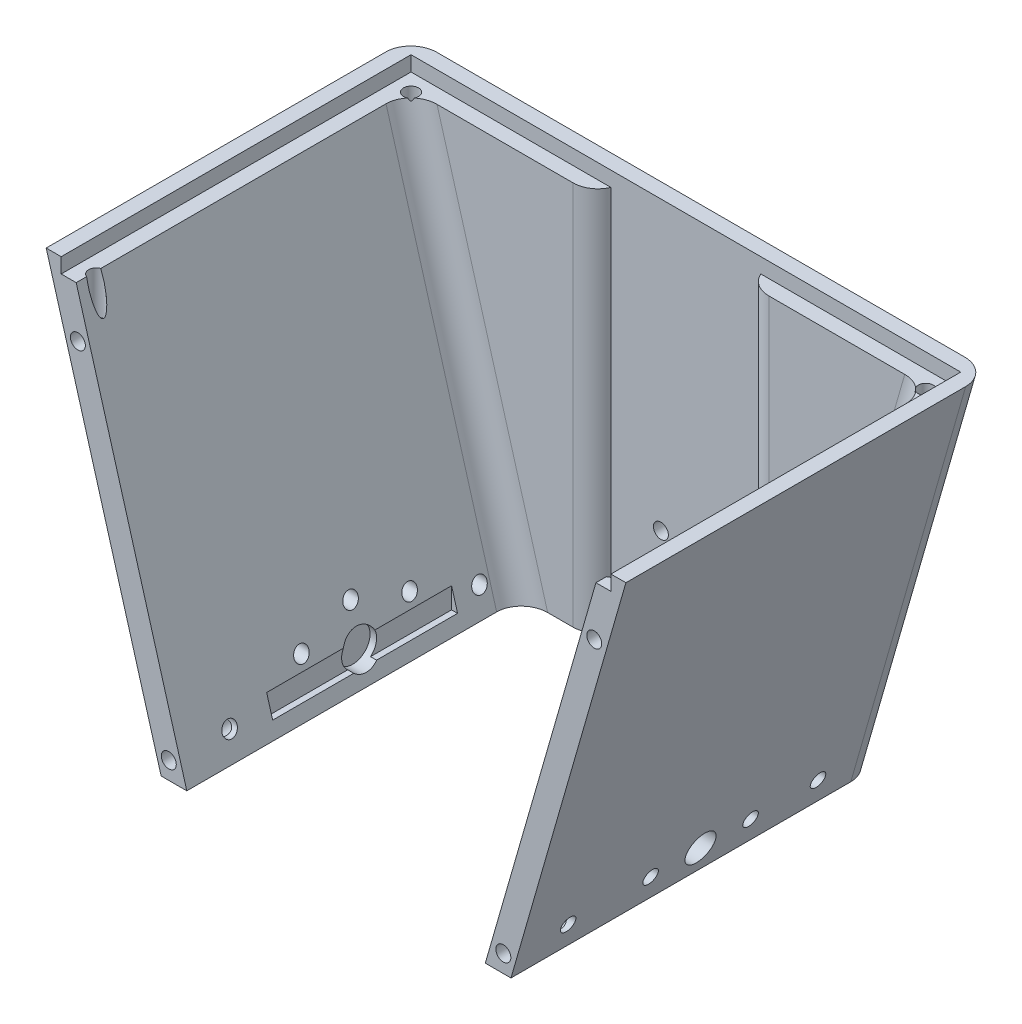
SolidWorks part; units mm, degrees
ref_plane "Front Plane" through (0, 0, 0) normal (0, 0, 1) x (1, 0, 0)
ref_plane "Top Plane" through (0, 0, 0) normal (0, 1, 0) x (1, 0, 0)
ref_plane "Right Plane" through (0, 0, 0) normal (1, 0, 0) x (0, 0, -1)
sketch "Sketch1" plane through (0, 0, 0) normal (0, 0, 1) x (1, 0, 0)
  line L0 (-70.4949, 0) -> (45.5051, 0)
  line L1 (-12.4949, -80) -> (22.5051, -80)
  line L2 (-12.4949, -80) -> (-47.4949, -80)
  line L3 (-70.4949, 0) -> (-47.4949, -80)
  line L4 (-12.4949, 0) -> (-12.4949, -303.8109) construction
  line L5 (45.5051, 0) -> (22.5051, -80)
  dimension "D1" = 116
  dimension "D2" = 35
  dimension "D3" = 35
  dimension "D4" = 80
  dimension "D5" = 73.96
  dimension "D6" = 73.96
extrude "Boss-Extrude1" add sketch "Sketch1" along normal blind 76
sketch "Sketch2" plane through (0, 0, 0) normal (0, 1, 0) x (1, 0, 0)
  line L0 (45.5051, 0) -> (-70.4949, 0) construction
  line L1 (-67.4949, -3) -> (42.5051, -3)
  line L2 (-67.4949, -3) -> (-67.4949, -73)
  line L3 (-67.4949, -73) -> (42.5051, -73)
  line L4 (42.5051, -3) -> (42.5051, -73)
  line L5 (45.5051, -76) -> (45.5051, 0) construction
  line L6 (45.5051, -76) -> (-70.4949, -76) construction
  line L7 (-70.4949, -76) -> (-70.4949, 0) construction
  dimension "D1" = 3
  dimension "D2" = 3
  dimension "D3" = 3
  dimension "D4" = 3
  dimension "D5" = 110
  dimension "D6" = 70
extrude "Cut-Extrude1" cut sketch "Sketch2" against normal blind 3
sketch "Sketch3" plane through (0, 0, 76) normal (0, 0, 1) x (1, 0, 0)
  line L0 (-42.0698, -81) -> (17.08, -81)
  line L1 (17.08, -81) -> (39.5051, -3)
  line L2 (39.5051, -3) -> (-64.4949, -3)
  line L3 (-64.4949, -3) -> (-42.0698, -81)
  line L5 (45.5051, 0) -> (-70.4949, 0) construction
  line L6 (-12.4949, -3) -> (-12.4949, -72.5382) construction
  line L7 (-67.4949, -3) -> (42.5051, -3) construction
  point P9 (-12.4949, 0)
  dimension "D1" = 73.96
  dimension "D2" = 73.96
  dimension "D3" = 104
  dimension "D4" = 0
  dimension "D5" = 0
  dimension "D6" = 78
extrude "Cut-Extrude2" cut sketch "Sketch3" against normal blind 70
sketch "Sketch4" plane through (0, 0, 0) normal (0, 1, 0) x (1, 0, 0)
  line L0 (45.5051, -76) -> (45.5051, 0) construction
  line L1 (-70.4949, -76) -> (45.5051, -76)
  line L2 (-70.4949, -76) -> (-70.4949, -73)
  line L3 (-70.4949, -73) -> (45.5051, -73)
  line L4 (45.5051, -76) -> (45.5051, -73)
extrude "Cut-Extrude3" cut sketch "Sketch4" against normal blind 95
fillet "Fillet1" radius 5 1 edges at (28.4363, -41.5, 6)
fillet "Fillet2" radius 5 1 edges at (-53.4261, -41.5, 6)
sketch "Sketch6" plane through (0, -3, 0) normal (0, 1, 0) x (1, 0, 0)
  line L0 (42.5051, -73) -> (42.5051, -3) construction
  line L1 (42.5051, -3) -> (-67.4949, -3) construction
  line L2 (-67.4949, -3) -> (-67.4949, -73) construction
  line L3 (-67.4949, -3) -> (-67.4949, -73) construction
  line L4 (-67.4949, -73) -> (-64.4949, -73) construction
  line L5 (42.5051, -73) -> (42.5051, -3) construction
  line L6 (39.5051, -73) -> (42.5051, -73) construction
  circle A0 centre (39.0051, -6.5) radius 1.5
  circle A1 centre (-63.9949, -6.5) radius 1.5
  circle A2 centre (-63.9949, -69.5) radius 1.5
  circle A3 centre (39.0051, -69.5) radius 1.5
  dimension "D1" = 3.5
  dimension "D2" = 3.5
  dimension "D3" = 3
  dimension "D4" = 3.5
  dimension "D5" = 3.5
  dimension "D6" = 3
  dimension "D7" = 3.5
  dimension "D8" = 3.5
  dimension "D9" = 3.5
  dimension "D10" = 3
  dimension "D11" = 3.5
  dimension "D12" = 3
extrude "Cut-Extrude4" cut sketch "Sketch6" against normal blind 10
sketch "Sketch7" plane through (0, -3, 0) normal (0, 1, 0) x (1, 0, 0)
  line L0 (34.3025, -6) -> (-59.2924, -6) construction
  line L1 (-27.4949, -9) -> (2.5051, -9)
  line L2 (-27.4949, -9) -> (-27.4949, -3)
  line L3 (-27.4949, -3) -> (2.5051, -3)
  line L4 (2.5051, -9) -> (2.5051, -3)
  line L5 (-27.4949, -9) -> (2.5051, -3) construction
  line L6 (-27.4949, -3) -> (2.5051, -9) construction
  line L7 (42.5051, -3) -> (-67.4949, -3) construction
  point P0 (-12.4949, -6)
  dimension "D1" = 30
extrude "Cut-Extrude5" cut sketch "Sketch7" against normal blind 93
fillet "Fillet3" radius 5 1 edges at (34.0051, -40, 0)
fillet "Fillet4" radius 5 1 edges at (-58.9949, -40, 0)
sketch "Sketch8" plane through (0, 0, 0) normal (0, 0, -1) x (-1, 0, 0)
  line L0 (12.4949, -80) -> (12.4949, -69) construction
  line L1 (42.2924, -80) -> (-17.3025, -80) construction
  line L3 (20.9949, -54) -> (3.9949, -54) construction
  line L4 (20.9949, -54) -> (20.9949, -69) construction
  line L5 (20.9949, -69) -> (3.9949, -69) construction
  line L6 (3.9949, -54) -> (3.9949, -69) construction
  circle A0 centre (7.4949, -65.5) radius 1.5
  circle A1 centre (7.4949, -57.5) radius 1.5
  circle A2 centre (17.4949, -57.5) radius 1.5
  circle A3 centre (17.4949, -65.5) radius 1.5
  dimension "D7" = 3
  dimension "D8" = 3.5
  dimension "D9" = 3.5
  dimension "D10" = 3
  dimension "D11" = 3
  dimension "D6" = 3
  dimension "D12" = 3.5
  dimension "D13" = 3.5
  dimension "D14" = 3.5
  dimension "D15" = 3.5
  dimension "D16" = 3.5
  dimension "D1" = 11
  dimension "D2" = 17
  dimension "D3" = 15
  dimension "D4" = 3.5
  dimension "D5" = 0
extrude "Cut-Extrude6" cut sketch "Sketch8" against normal blind 93
sketch "Sketch9" plane through (0, 0, 73) normal (0, 0, 1) x (1, 0, 0)
  line L0 (-42.3573, -80) -> (-47.4949, -80) construction
  line L1 (-64.4949, -3) -> (-42.3573, -80) construction
  line L2 (22.5051, -80) -> (17.3675, -80) construction
  line L3 (39.5051, -3) -> (17.3675, -80) construction
  line L4 (42.5051, -3) -> (2.5051, -3) construction
  line L5 (45.5051, 0) -> (22.5051, -80) construction
  line L6 (-67.4949, -3) -> (-64.4949, -3) construction
  line L7 (-47.4949, -80) -> (-70.4949, 0) construction
  circle A0 centre (20.975, -76.5) radius 1.5
  circle A1 centre (-45.9649, -76.5) radius 1.5
  circle A2 centre (-64.1562, -13) radius 1.5
  circle A3 centre (39.1663, -13) radius 1.5
  point P20 (-65.9949, -3)
  dimension "D1" = 3
  dimension "D2" = 3
  dimension "D3" = 3
  dimension "D4" = 3
  dimension "D5" = 3.5
  dimension "D6" = 2.5
  dimension "D7" = 3.5
  dimension "D8" = 2.5
  dimension "D9" = 10
  dimension "D10" = 2.5
  dimension "D11" = 10
  dimension "D12" = 2.5
extrude "Cut-Extrude7" cut sketch "Sketch9" against normal blind 15
fillet "Fillet5" radius 5 1 edges at (2.5051, -41.5, 6)
fillet "Fillet6" radius 5 1 edges at (-27.4949, -41.5, 6)
sketch "Sketch10" plane through (0, 0, 0) normal (1, 0, 0) x (0, 0, -1)
  line L0 (-73, 0) -> (-73, -80) construction
  line L1 (-73, -80) -> (-5, -80) construction
  circle A0 centre (-63, -75) radius 1.5
  circle A1 centre (-13, -75) radius 1.5
  dimension "D1" = 3
  dimension "D2" = 3
  dimension "D3" = 10
  dimension "D4" = 5
  dimension "D5" = 50
  dimension "D6" = 5
extrude "Cut-Extrude8" cut sketch "Sketch10" against normal blind 70 and the other way blind 30
sketch "front" plane through (0, 0, 73) normal (0, 0, 1) x (1, 0, 0)
  line L0 (-47.4949, -80) -> (22.5051, -80)
  line L1 (22.5051, -80) -> (45.5051, 0)
  line L2 (45.5051, 0) -> (-70.4949, 0)
  line L3 (-70.4949, 0) -> (-47.4949, -80)
  circle A0 centre (-64.1562, -13) radius 1.5
  circle A1 centre (39.1663, -13) radius 1.5
  circle A2 centre (20.975, -76.5) radius 1.5
  circle A3 centre (-45.9649, -76.5) radius 1.5
sketch "Sketch12" plane through (0, 0, 0) normal (1, 0, 0) x (0, 0, -1)
  line L0 (0, -80) -> (-73, -80) construction
  circle A0 centre (-36.5, -74.5) radius 3.5
  dimension "D1" = 7
  dimension "D2" = 5.5
extrude "Cut-Extrude9" cut sketch "Sketch12" against normal blind 45.6894
sketch "Sketch13" plane through (0, 0, 0) normal (1, 0, 0) x (0, 0, -1)
  line L0 (0, -80) -> (-73, -80) construction
  circle A0 centre (-36.5, -75) radius 3
  dimension "D1" = 6
  dimension "D2" = 5
extrude "Cut-Extrude10" cut sketch "Sketch13" along normal blind 39.6332
sketch "Sketch15" plane through (0, 0, 0) normal (1, 0, 0) x (0, 0, -1)
  line L0 (-40, -74.5) -> (-55, -74.5) construction
  line L1 (-33, -74.5) -> (-18, -74.5) construction
  line L2 (-55, -74.5) -> (-53.7329, -74.5) construction
  line L3 (-55, -77.15) -> (-18, -77.15)
  line L4 (-55, -77.15) -> (-55, -71.85)
  line L5 (-55, -71.85) -> (-18, -71.85)
  line L6 (-18, -77.15) -> (-18, -71.85)
  circle A0 centre (-36.5, -74.5) radius 3.5 construction
  circle A1 centre (-36.5, -74.5) radius 3.5 construction
  dimension "D1" = 15
  dimension "D2" = 15
  dimension "D3" = 5.3
  dimension "D4" = 0
sketch "Sketch16" plane through (0, 0, 73) normal (0, 0, 1) x (1, 0, 0)
  line L1 (-64.4949, -3) -> (-42.3573, -80) construction
  line L2 (0, -77.15) -> (0, -71.85) construction
  line L3 (0, -77.15) -> (0, -71.85) construction
  line L4 (0, -71.85) -> (-44.7005, -71.85) construction
  dimension "D1" = 44.7005
extrude "Cut-Extrude13" cut sketch "Sketch15" against normal blind 44.38
sketch "Sketch17" plane through (0, 0, 0) normal (1, 0, 0) x (0, 0, -1)
  line L0 (-55, -72.9647) -> (-39.6453, -72.9647) construction
  line L1 (-33.3547, -72.9647) -> (-18, -72.9647) construction
  circle A0 centre (-47.3226, -70.4647) radius 1.5
  circle A1 centre (-25.6774, -70.4647) radius 1.5
  point P4 (-47.3226, -72.9647)
  dimension "D1" = 3
  dimension "D2" = 3
  dimension "D3" = 2.5
  dimension "D4" = 2.5
extrude "Cut-Extrude14" cut sketch "Sketch17" against normal blind 58.7005
sketch "Sketch18" plane through (0, 0, 0) normal (1, 0, 0) x (0, 0, -1)
  circle A0 centre (-36.5, -67) radius 1.5
  circle A1 centre (-36.5, -74.5) radius 3.5 construction
  dimension "D1" = 3
  dimension "D2" = 7.5
extrude "Cut-Extrude15" cut sketch "Sketch18" against normal blind 58.7005
sketch "Sketch19" plane through (0, 0, 0) normal (1, 0, 0) x (0, 0, -1)
  circle A0 centre (-46.5, -75) radius 1.5
  circle A1 centre (-26.5, -75) radius 1.5
  circle A2 centre (-36.5, -75) radius 3 construction
  dimension "D1" = 3
  dimension "D2" = 3
  dimension "D3" = 10
  dimension "D4" = 10
extrude "Cut-Extrude16" cut sketch "Sketch19" along normal blind 58.7005
sketch "Sketch20" plane through (0, 0, 73) normal (0, 0, 1) x (1, 0, 0)
  line L0 (-42.3573, -80) -> (17.3675, -80)
  line L1 (17.3675, -80) -> (19.8113, -71.5)
  line L2 (17.3675, -80) -> (39.5051, -3) construction
  line L3 (19.8113, -71.5) -> (-44.8011, -71.5)
  line L4 (-64.4949, -3) -> (-42.3573, -80) construction
  line L5 (-44.8011, -71.5) -> (-42.3573, -80)
  circle A0 centre (-45.9649, -76.5) radius 1.5 construction
  dimension "D1" = 5
